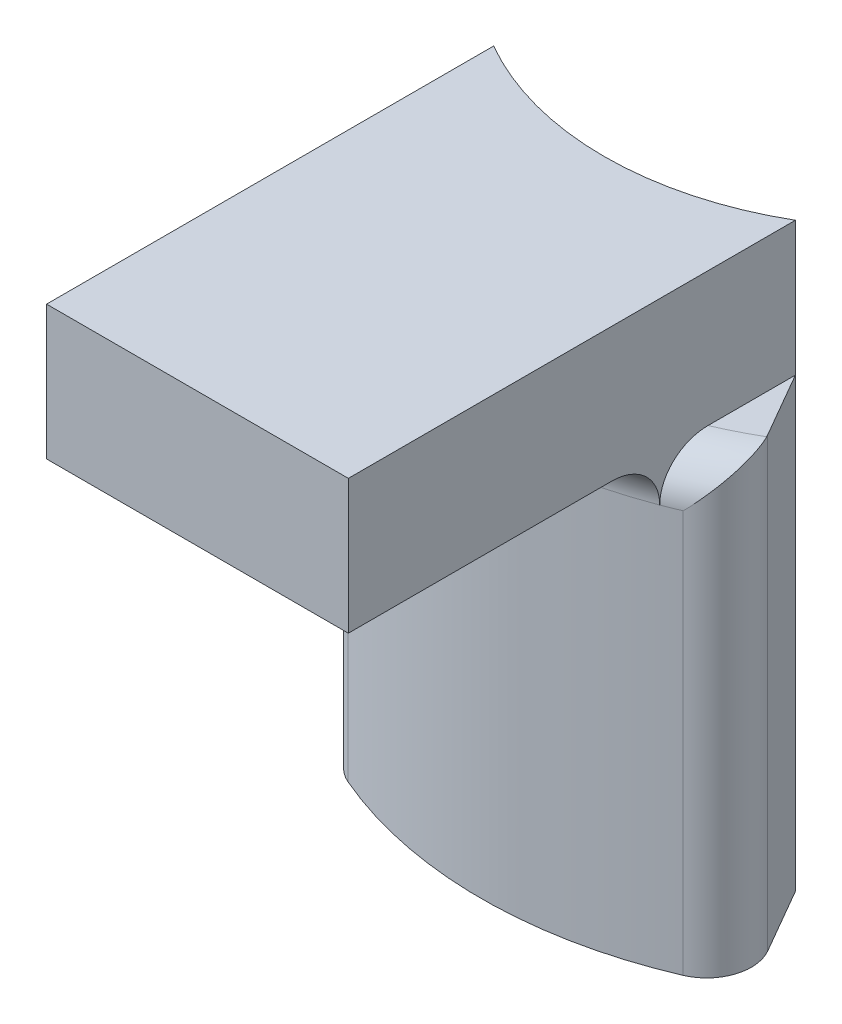
SolidWorks part; units mm, degrees
ref_plane "Front Plane" through (0, 0, 0) normal (0, 0, 1) x (1, 0, 0)
ref_plane "Top Plane" through (0, 0, 0) normal (0, 1, 0) x (1, 0, 0)
ref_plane "Right Plane" through (0, 0, 0) normal (1, 0, 0) x (0, 0, -1)
sketch "Sketch1" plane through (0, 0, 0) normal (0, 1, 0) x (1, 0, 0)
  line L0 (0, 0) -> (-4.75, -8.2272) construction
  line L1 (-4.75, -8.2272) -> (4.75, -8.2272) construction
  line L2 (4.75, -8.2272) -> (0, 0) construction
  line L3 (3.375, -5.8457) -> (4.75, -8.2272)
  line L4 (-3.375, -5.8457) -> (-4.75, -8.2272)
  circle A0 centre (0, 0) radius 12.5 construction
  circle A1 centre (0, 0) radius 6.75 construction
  circle A2 centre (0, 0) radius 9.5 construction
  arc A3 (3.375, -5.8457) -> (-3.375, -5.8457) centre (0, 0) cw
  arc A4 (4.75, -8.2272) -> (-4.75, -8.2272) centre (0, 0) cw
  point P9 (0, 0)
  dimension "D1" = 25
  dimension "D2" = 13.5
  dimension "D4" = 9.5
  dimension "D3" = 3
extrude "Boss-Extrude1" add sketch "Sketch1" along normal blind 10 contours A4 L3 A3 L4
sketch "Sketch2" plane through (0, 10, 0) normal (0, 1, 0) x (1, 0, 0)
  line L0 (-3.375, -5.8457) -> (-3.375, -15.8457)
  line L1 (-3.375, -15.8457) -> (3.375, -15.8457)
  line L2 (3.375, -15.8457) -> (3.375, -5.8457)
  arc A0 (3.375, -5.8457) -> (-3.375, -5.8457) centre (0, 0) cw
  arc A1 (-3.375, -5.8457) -> (3.375, -5.8457) centre (0, 0) ccw construction
  point P7 (0, -6.75)
  point P11 (0, -6.75)
  dimension "D1" = 10
extrude "Boss-Extrude2" add sketch "Sketch2" along normal blind 3
fillet "Fillet1" radius 1 1 edges at (0, 10, 9.5)
fillet "Fillet2" radius 1 1 edges at (-4.0756, 10, 8.5813)
fillet "Fillet3" radius 1 2 edges at (-4.75, 4.5, 8.2272) (4.0756, 10, 8.5813)
fillet "Fillet4" radius 1 1 edges at (4.75, 4.5, 8.2272)
